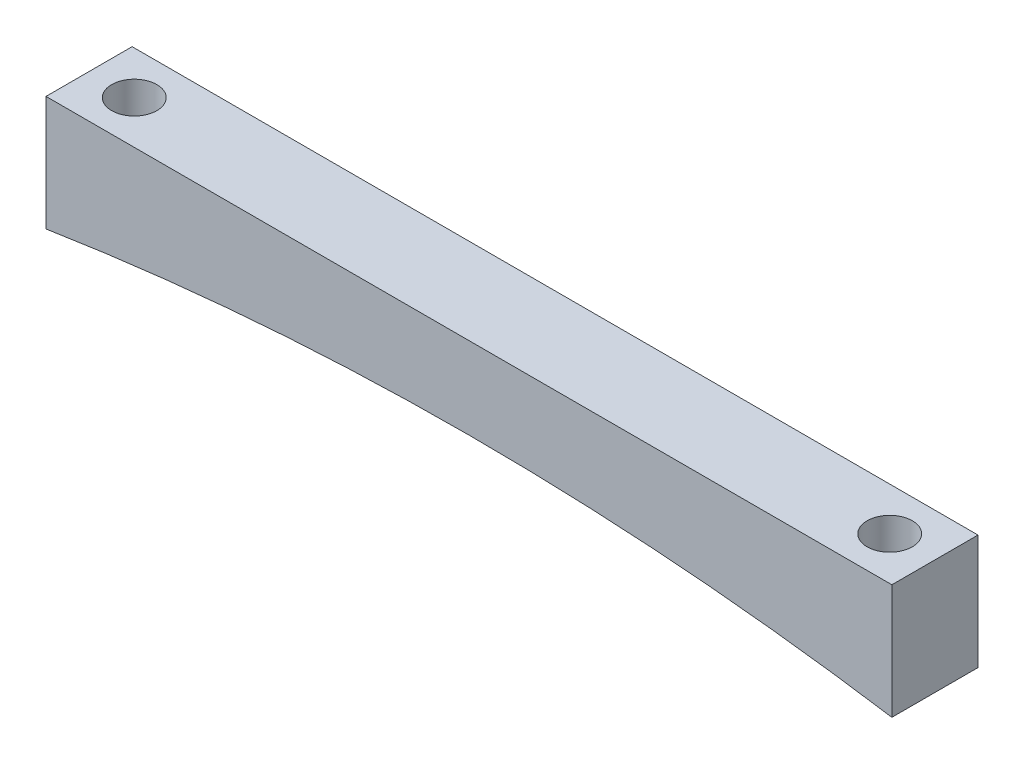
SolidWorks part; units mm, degrees
ref_plane "Front Plane" through (0, 0, 0) normal (0, 0, 1) x (1, 0, 0)
ref_plane "Top Plane" through (0, 0, 0) normal (0, 1, 0) x (1, 0, 0)
ref_plane "Right Plane" through (0, 0, 0) normal (1, 0, 0) x (0, 0, -1)
sketch "Sketch1" plane through (0, 0, 0) normal (0, 0, 1) x (1, 0, 0)
  line L0 (-37.4205, 0) -> (37.4205, 0)
  line L1 (-33.4205, -2.54) -> (33.4205, -2.54) construction
  line L2 (0, 0) -> (0, -4.6068) construction
  line L3 (37.4205, 0) -> (37.4205, -10.16)
  line L4 (-37.4205, 0) -> (-37.4205, -10.16)
  arc A0 (-37.4205, -10.16) -> (37.4205, -10.16) centre (0, -248.5408) cw
  point P4 (0, 0)
  point P9 (0, -2.54)
  point P12 (-38.6638, -24.7934)
  point P13 (37.4205, -28.4662)
  dimension "D4" = 241.3
  dimension "D1" = 66.8409
  dimension "D2" = 2.54
  dimension "D3" = 4
  dimension "D5" = 10.16
extrude "Boss-Extrude1" add sketch "Sketch1" along normal blind 7.62
sketch "Sketch2" plane through (0, 0, 0) normal (0, 1, 0) x (1, 0, 0)
  line L1 (-33.4205, 0) -> (-33.4205, -7.62) construction
  line L2 (-37.4205, 0) -> (37.4205, 0) construction
  line L3 (37.4205, -7.62) -> (-37.4205, -7.62) construction
  line L4 (33.4205, 0) -> (33.4205, -7.62) construction
  circle A0 centre (-33.4205, -3.81) radius 2
  circle A1 centre (33.4205, -3.81) radius 2
  circle A2 centre (-33.4205, -3.81) radius 3 construction
  point P5 (33.4205, -3.81)
  point P7 (-33.4205, -3.81)
  dimension "D1" = 4
  dimension "D2" = 6
extrude "Cut-Extrude1" cut sketch "Sketch2" against normal blind 6.5
